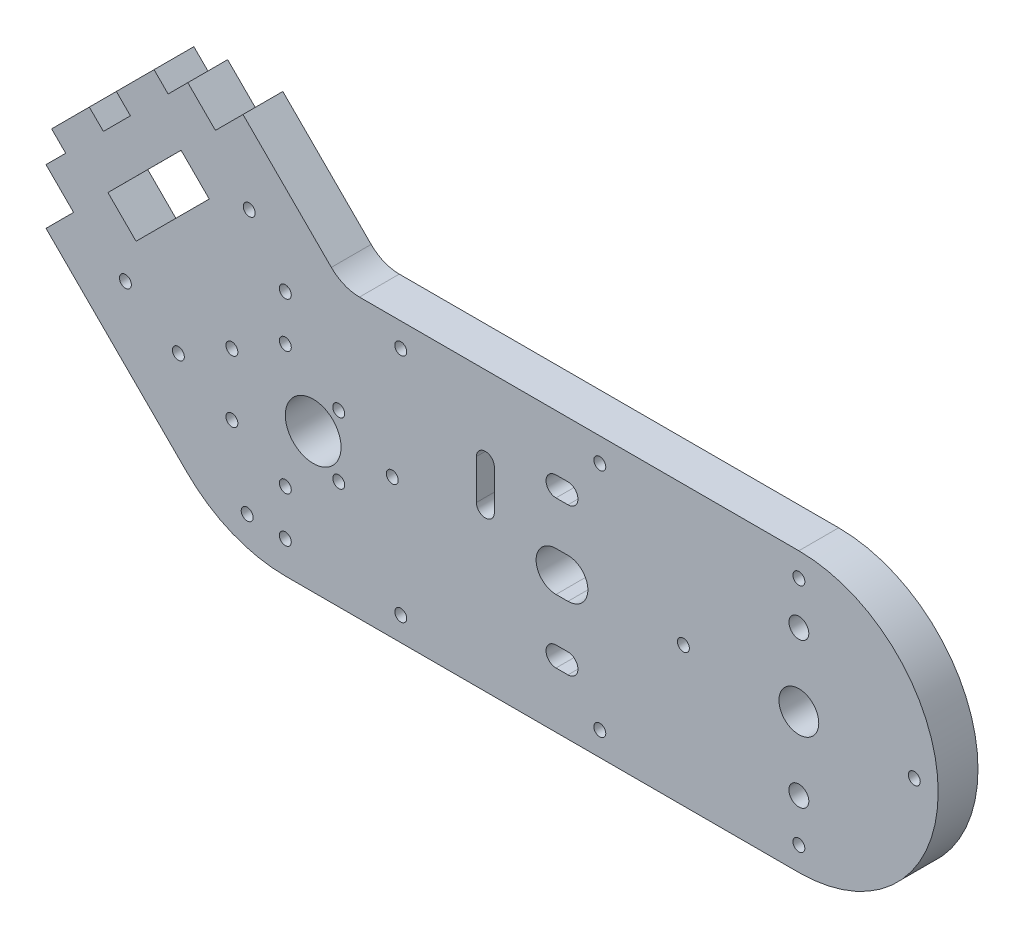
SolidWorks part; units mm, degrees
ref_plane "Front Plane" through (0, 0, 0) normal (0, 0, 1) x (1, 0, 0)
ref_plane "Top Plane" through (0, 0, 0) normal (0, 1, 0) x (1, 0, 0)
ref_plane "Right Plane" through (0, 0, 0) normal (1, 0, 0) x (0, 0, -1)
sketch "Sketch1" plane through (0, 0, 0) normal (0, 0, 1) x (1, 0, 0)
  line L0 (0, -35) -> (-129, -35)
  line L4 (0, 35) -> (-110.37, 35)
  line L9 (-58, 0) -> (-61, 0) construction
  line L10 (-58, -5) -> (-61, -5)
  line L11 (-58, 5) -> (-61, 5)
  line L13 (-58, 18.5) -> (-61, 18.5) construction
  line L14 (-58, 16) -> (-61, 16)
  line L15 (-58, 21) -> (-61, 21)
  line L17 (-58, -18.5) -> (-61, -18.5) construction
  line L18 (-58, -21) -> (-61, -21)
  line L19 (-58, -16) -> (-61, -16)
  line L20 (-78.75, 5) -> (-78.75, 15) construction
  line L21 (-81, 5) -> (-81, 15)
  line L22 (-76.5, 5) -> (-76.5, 15)
  line L25 (0, 0) -> (-129, 0) construction
  line L27 (-189.1079, 10.5847) -> (-182.1808, 17.5169)
  line L28 (-182.1808, 17.5169) -> (-146.5556, 53.168) construction
  line L29 (-146.5556, 53.168) -> (-139.6285, 60.1002)
  line L30 (-146.5556, 53.168) -> (-153.4878, 60.0952)
  line L31 (-182.1808, 17.5169) -> (-189.113, 24.444)
  line L32 (-189.113, 24.444) -> (-184.1651, 29.3955)
  line L33 (-184.1651, 29.3955) -> (-187.7019, 32.9298)
  line L34 (-153.4878, 60.0952) -> (-158.4357, 55.1436)
  line L35 (-158.4357, 55.1436) -> (-161.9726, 58.6778)
  line L36 (-187.7019, 32.9298) -> (-178.2301, 42.4085)
  line L37 (-184.1651, 29.3955) -> (-158.4357, 55.1436) construction
  line L38 (-178.2301, 42.4085) -> (-174.6933, 38.8742)
  line L39 (-161.9726, 58.6778) -> (-171.4443, 49.1992)
  line L40 (-171.4443, 49.1992) -> (-167.9075, 45.6649)
  line L41 (-174.6933, 38.8742) -> (-167.9075, 45.6649)
  line L43 (-189.1079, 10.5847) -> (-153.7397, -24.7578)
  line L44 (-171.3004, 42.2696) -> (-129, 0) construction
  line L45 (-139.6285, 60.1002) -> (-117.4393, 37.9271)
  line L46 (-173.5573, 26.1467) -> (-155.1792, 44.5382)
  line L47 (-155.1792, 44.5382) -> (-148.1081, 37.4671)
  line L48 (-148.1081, 37.4671) -> (-166.4929, 19.0823)
  line L49 (-166.4929, 19.0823) -> (-173.5573, 26.1467)
  line L54 (-129, 0) -> (-138.5766, -26.3114) construction
  line L55 (-129, 26.8701) -> (-129, -26.8701) construction
  line L56 (-155.8701, 0) -> (-102.1299, 0) construction
  line L57 (-129, 0) -> (-129, 15.5) construction
  line L58 (-129, 0) -> (-149.42, 0) construction
  line L59 (-122, 0) -> (-142.42, 0) construction
  line L60 (-142.42, 0) -> (-142.42, -7.7559) construction
  line L61 (-142.42, 7.7559) -> (-142.42, 0) construction
  line L62 (-122, 0) -> (-122, -7.7559) construction
  line L63 (-122, -7.7559) -> (-115.58, -7.7559) construction
  line L64 (-122, 0) -> (-122, 7.7559) construction
  line L65 (-122, 7.7559) -> (-115.58, 7.7559) construction
  line L66 (0, 0) -> (0, 18.25) construction
  circle A0 centre (0, 0) radius 5
  circle A1 centre (29, 0) radius 1.5
  circle A2 centre (0, -18.25) radius 2.5
  circle A3 centre (0, 18.25) radius 2.5
  arc A4 (0, -35) -> (0, 35) centre (0, 0) ccw
  circle A5 centre (0, 29) radius 1.5
  circle A6 centre (0, -29) radius 1.5
  circle A7 centre (-50, -29) radius 1.5
  circle A8 centre (-50, 29) radius 1.5
  circle A9 centre (-100, -29) radius 1.5
  circle A10 centre (-100, 29) radius 1.5
  arc A11 (-58, -5) -> (-58, 5) centre (-58, 0) ccw
  arc A12 (-61, 5) -> (-61, -5) centre (-61, 0) ccw
  arc A13 (-58, 16) -> (-58, 21) centre (-58, 18.5) ccw
  arc A14 (-61, 21) -> (-61, 16) centre (-61, 18.5) ccw
  arc A15 (-58, -21) -> (-58, -16) centre (-58, -18.5) ccw
  arc A16 (-61, -16) -> (-61, -21) centre (-61, -18.5) ccw
  circle A17 centre (-29, 0) radius 1.5
  arc A18 (-81, 5) -> (-76.5, 5) centre (-78.75, 5) ccw
  arc A19 (-76.5, 15) -> (-81, 15) centre (-78.75, 15) ccw
  arc A22 (-129, -35) -> (-153.7397, -24.7578) centre (-129, 0) cw
  arc A23 (-117.4393, 37.9271) -> (-110.37, 35) centre (-110.37, 45) ccw
  circle A27 centre (-169.167, 9.0363) radius 1.5
  circle A28 centre (-138.0656, 40.1604) radius 1.5
  circle A29 centre (-122, 0) radius 7
  circle A30 centre (-129, 26.8701) radius 1.5
  circle A31 centre (-155.8701, 0) radius 1.5
  circle A32 centre (-129, -26.8701) radius 1.5
  circle A33 centre (-102.1299, 0) radius 1.5
  circle A34 centre (-138.5766, -26.3114) radius 1.5
  circle A35 centre (-129, 15.5) radius 1.5
  circle A37 centre (-129, -15.5) radius 1.5
  circle A38 centre (-142.42, 7.7559) radius 1.5
  circle A39 centre (-142.42, -7.7559) radius 1.5
  circle A40 centre (-115.58, -7.7559) radius 1.5
  circle A41 centre (-115.58, 7.7559) radius 1.5
  point P13 (0, -29)
  point P29 (-59.5, 0)
  point P37 (-59.5, 18.5)
  point P45 (-59.5, -18.5)
  point P54 (-78.75, 10)
  point P74 (-102.28, 58.871)
  point P79 (-122, 0)
  point P86 (-164.3682, 35.3424)
  point P91 (-155.9618, 57.6194)
  dimension "D1" = 10
  dimension "D2" = 5
  dimension "D3" = 5
  dimension "D4" = 70
  dimension "D5" = 3
  dimension "D6" = 3
  dimension "D7" = 3
  dimension "D8" = 3
  dimension "D9" = 3
  dimension "D10" = 3
  dimension "D11" = 3
  dimension "D14" = 50
  dimension "D12" = 35
  dimension "D13" = 35
  dimension "D19" = 5
  dimension "D22" = 36.4
  dimension "D35" = 10
  dimension "D33" = 3
  dimension "D37" = 3
  dimension "D36" = 13
  dimension "D39" = 38
  dimension "D41" = 3
  dimension "D42" = 3
  dimension "D43" = 3
  dimension "D44" = 3
  dimension "D46" = 3
  dimension "D47" = 3
  dimension "D48" = 3
  dimension "D49" = 3
  dimension "D50" = 3
  dimension "D51" = 3
  dimension "D52" = 3
  dimension "D55" = 26.7761
  dimension "D15" = 129
  dimension "D16" = 58
  dimension "D17" = 11
  dimension "D18" = 4.5
  dimension "D20" = 10
  dimension "D21" = 110.37
  dimension "D23" = 50.4
  dimension "D24" = 13.4
  dimension "D25" = 9.8
  dimension "D26" = 9.8
  dimension "D27" = 7
  dimension "D28" = 9.8
  dimension "D29" = 9.8
  dimension "D30" = 5
  dimension "D31" = 5
  dimension "D32" = 13.4
  dimension "D34" = 31.3689
  dimension "D38" = 7
  dimension "D40" = 38
  dimension "D45" = 28
  dimension "D53" = 18.25
  dimension "D54" = 18.25
  dimension "D56" = 7.6513
extrude "Boss-Extrude1" add sketch "Sketch1" along normal blind 10
